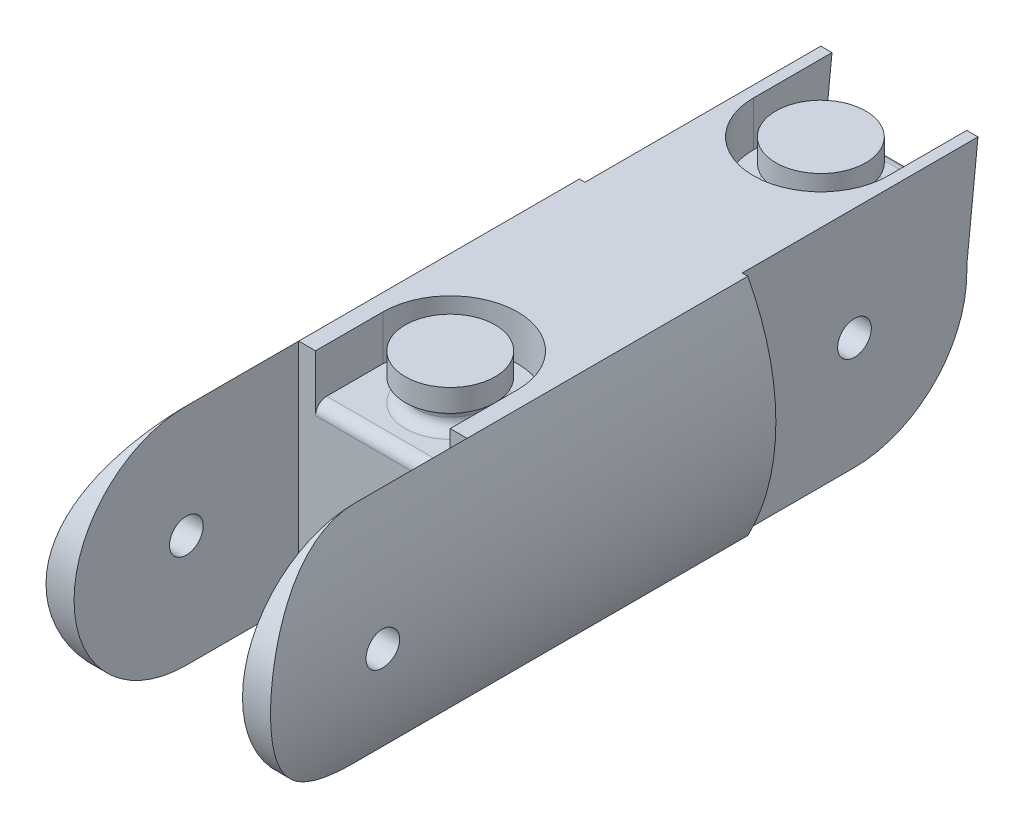
SolidWorks part; units mm, degrees
ref_plane "Alzado" through (0, 0, 0) normal (0, 0, 1) x (1, 0, 0)
ref_plane "Planta" through (0, 0, 0) normal (0, 1, 0) x (1, 0, 0)
ref_plane "Vista lateral" through (0, 0, 0) normal (1, 0, 0) x (0, 0, -1)
sketch "Croquis2" plane through (0, 0, 0) normal (0, 0, 1) x (1, 0, 0)
  line L5 (-7.5, -10) -> (7.5, -10)
  line L7 (-7.5, 10) -> (7.5, 10)
  line L9 (-7.5, -10) -> (7.5, 10) construction
  line L10 (-7.5, 10) -> (7.5, -10) construction
  arc A2 (-7.5, 10) -> (-7.5, -10) centre (11.25, 0) ccw
  arc A3 (7.5, -10) -> (7.5, 10) centre (-11.25, 0) ccw
  point P0 (0, 0)
  dimension "D1" = 15
  dimension "D2" = 20
extrude "Saliente-Extruir2" add sketch "Croquis2" along normal blind 45
sketch "Croquis4" plane through (0, 0, 0) normal (0, 0, -1) x (-1, 0, 0)
  line L1 (7.5, -10) -> (-7.5, -10) construction
  circle A0 centre (0, -7) radius 1.5
  dimension "D2" = 3
  dimension "D1" = 3
extrude "Cortar-Extruir1" cut sketch "Croquis4" against normal blind 50
sketch "Croquis3" plane through (0, 0, 0) normal (0, 0, -1) x (-1, 0, 0)
  line L8 (7.5, -10) -> (-7.5, -10) construction
  line L10 (7, 10) -> (7, -10)
  line L11 (7, -10) -> (3, -10)
  line L12 (-7, 10) -> (-7, -10)
  line L13 (7, 10) -> (-7, -10) construction
  line L14 (7, -10) -> (-7, 10) construction
  line L16 (3, -3) -> (3, -10)
  line L17 (-3, -10) -> (-7, -10)
  line L19 (-3, -3) -> (3, -3)
  line L20 (-3, -3) -> (-3, -10)
  line L21 (-7, 10) -> (7, 10)
  point P0 (0, 0)
  dimension "D1" = 14
  dimension "D2" = 4
  dimension "D3" = 4
  dimension "D4" = 7
extrude "Saliente-Extruir3" add sketch "Croquis3" along normal blind 20
sketch "Croquis8" plane through (-7, 0, 0) normal (-1, 0, 0) x (0, 0, 1)
  line L0 (-20, -10) -> (-20, 10) construction
  line L1 (-20, -10) -> (0, -10) construction
  circle A0 centre (-10, 0) radius 1.5
  point P4 (-20, 0)
  dimension "D1" = 3
  dimension "D2" = 10
  dimension "D3" = 10
extrude "Cortar-Extruir4" cut sketch "Croquis8" against normal blind 14
fillet "Redondeo1" radius 10 2 edges at (-5, -10, -20) (5, -10, -20)
sketch "Croquis6" plane through (0, 0, 45) normal (0, 0, 1) x (1, 0, 0)
  line L1 (-7.5, 10) -> (7.5, 10)
  line L2 (-7.5, 10) -> (-7.5, -10)
  line L3 (-7.5, -10) -> (7.5, -10)
  line L4 (7.5, 10) -> (7.5, -10)
extrude "Cortar-Extruir2" cut sketch "Croquis6" against normal blind 20
sketch "Croquis7" plane through (0, 0, 0) normal (1, 0, 0) x (0, 0, -1)
  line L0 (-45, 10) -> (-45, -10) construction
  line L2 (-35, -10) -> (-50, -10)
  line L4 (-35, 10) -> (-50, 10)
  line L5 (-50, -10) -> (-50, 10)
  arc A0 (-35, 10) -> (-35, -10) centre (-35, 0) ccw
  circle A1 centre (-35, 0) radius 1.5
  dimension "D3" = 10
  dimension "D4" = 3
  dimension "D1" = 10
  dimension "D2" = 15
  dimension "D5" = 20
extrude "Cortar-Extruir3" cut sketch "Croquis7" against normal through all both and the other way through all
sketch "Sketch1" plane through (0, 10, 0) normal (0, 1, 0) x (1, 0, 0)
  line L0 (-7, 20) -> (7, 20) construction
  line L1 (7.5, -25) -> (-7.5, -25) construction
  line L4 (-6, 14) -> (-6, 20)
  line L5 (-6, 20) -> (6, 20)
  line L6 (6, 14) -> (6, 20)
  line L8 (-6, -19) -> (-6, -25)
  line L9 (-6, -25) -> (6, -25)
  line L10 (6, -19) -> (6, -25)
  arc A0 (6, -19) -> (-6, -19) centre (0, -19) ccw
  arc A1 (-6, 14) -> (6, 14) centre (0, 14) ccw
  dimension "D3" = 12
  dimension "D4" = 12
  dimension "D1" = 6
  dimension "D2" = 6
extrude "Cut-Extrude1" cut sketch "Sketch1" against normal blind 4
sketch "Sketch2" plane through (0, 6, 0) normal (0, 1, 0) x (1, 0, 0)
  circle A0 centre (0, -19) radius 3
  circle A1 centre (0, 14) radius 3
  dimension "D1" = 6
  dimension "D2" = 6
extrude "Boss-Extrude1" add sketch "Sketch2" along normal blind 2
sketch "Sketch3" plane through (0, 8, 0) normal (0, 1, 0) x (1, 0, 0)
  circle A0 centre (0, -19) radius 4
  circle A1 centre (0, 14) radius 4
  dimension "D1" = 8
  dimension "D2" = 8
extrude "Boss-Extrude2" add sketch "Sketch3" along normal blind 2
fillet "Fillet2" radius 1 4 edges at (0, 8, -11) (0, 6, -11) (0, 8, 22) (0, 6, 22)
fillet "Fillet3" radius 1 2 edges at (0, 6, -20) (0, 6, 25)
fillet "Fillet4" radius 1 2 edges at (-1.5, -7, 0) (1.5, -7, 25)
sketch "Sketch4" plane through (7, 0, 0) normal (1, 0, 0) x (0, 0, -1)
  line L0 (20, 10) -> (21, 10)
  line L1 (21, 10) -> (19.6702, -2.5469)
  line L2 (19.6702, -2.5469) -> (20, 10)
  arc A0 (10, -10) -> (20, 0) centre (10, 0) ccw construction
  dimension "D1" = 1
sketch "Sketch5" plane through (-7, 0, 0) normal (-1, 0, 0) x (0, 0, 1)
  line L0 (-20, 10) -> (-21, 10)
  line L1 (-21, 10) -> (-19.6702, -2.5469)
  line L2 (-19.6702, -2.5469) -> (-20, 10)
extrude "Boss-Extrude3" add sketch "Sketch5" against normal blind 1
extrude "Boss-Extrude4" add sketch "Sketch4" against normal blind 1
sketch "Sketch6" plane through (0, 0, 0) normal (0, 0, -1) x (-1, 0, 0)
  line L0 (-3, -4) -> (3, -4)
  line L1 (-3, -2) -> (3, -2)
  line L2 (-7, 0) -> (-7, -10) construction
  line L3 (3, -10) -> (-3, -10) construction
  arc A0 (-3, -2) -> (-3, -4) centre (-3, -3) ccw
  arc A1 (3, -4) -> (3, -2) centre (3, -3) ccw
  dimension "D1" = 2
  dimension "D2" = 2
  dimension "D3" = 6
  dimension "D4" = 4
  dimension "D5" = 8
extrude "Cut-Extrude2" cut sketch "Sketch6" along normal blind 40 from offset 20 offset against normal yes
sketch "Sketch7" plane through (0, -10, 0) normal (0, -1, 0) x (1, 0, 0)
  line L0 (7, -20) -> (-7, -20) construction
  line L1 (-4, 0) -> (4, 0)
  line L2 (-4, 0) -> (-4, -20)
  line L3 (-4, -20) -> (4, -20)
  line L4 (4, 0) -> (4, -20)
  line L5 (-7, -10) -> (-7, 0) construction
  dimension "D1" = 8
  dimension "D2" = 3
extrude "Cut-Extrude3" cut sketch "Sketch7" against normal blind 7
fillet "Fillet5" radius 0.5 3 edges at (3.7071, -3.7071, 0) (-3.7071, -3.7071, 0) (0, -4, 0)
